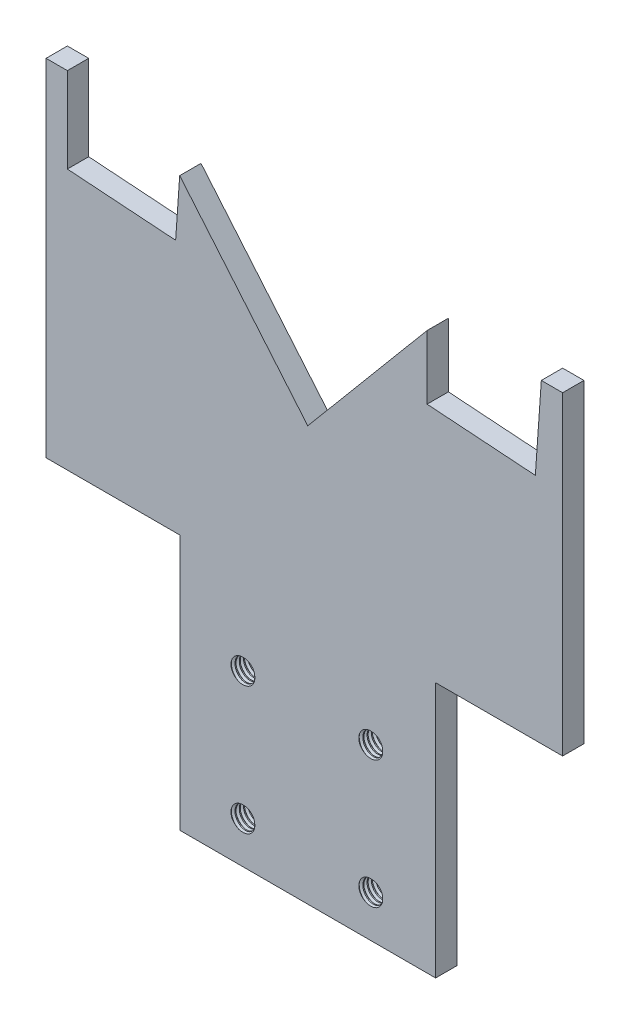
SolidWorks part; units mm, degrees
ref_plane "Front Plane" through (0, 0, 0) normal (0, 0, 1) x (1, 0, 0)
ref_plane "Top Plane" through (0, 0, 0) normal (0, 1, 0) x (1, 0, 0)
ref_plane "Right Plane" through (0, 0, 0) normal (1, 0, 0) x (0, 0, -1)
sketch "Sketch1" plane through (0, 0, 0) normal (0, 0, 1) x (1, 0, 0)
  line L1 (-35.9396, -69.828) -> (26.5158, -69.828)
  line L5 (0, 53.616) -> (35.56, 95.9948)
  line L6 (-39.37, 81.81) -> (-38.1613, 99.0949)
  line L7 (0, -55) -> (0, 55) construction
  line L10 (35.56, 95.9948) -> (35.56, 76.984)
  line L11 (35.56, 76.984) -> (67.818, 74.7283)
  line L12 (67.818, 74.7283) -> (69.5941, 100.1283)
  line L13 (69.5941, 100.1283) -> (75.9441, 100.1283)
  line L14 (26.5158, -69.828) -> (75.9441, -69.828)
  line L15 (75.9441, -69.828) -> (75.9441, 100.1283)
  line L18 (-39.37, 81.81) -> (-71.628, 84.0657)
  line L19 (-71.628, 84.0657) -> (-71.628, 109.4657)
  line L20 (-71.628, 109.4657) -> (-77.978, 109.4657)
  line L21 (-77.978, 109.4657) -> (-77.978, -69.828)
  line L22 (-77.978, -69.828) -> (-35.9396, -69.828)
  line L23 (0, 53.616) -> (-38.1613, 99.0949)
  point P0 (0, 0)
  dimension "D2" = 40
  dimension "D3" = 123.444
  dimension "D4" = 4
  dimension "D5" = 4
  dimension "D6" = 90
  dimension "D7" = 94
  dimension "D8" = 32.258
  dimension "D9" = 32.258
  dimension "D10" = 4
  dimension "D11" = 35.56
  dimension "D12" = 39.37
  dimension "D13" = 146.812
  dimension "D14" = 151.638
  dimension "D15" = 90
  dimension "D16" = 40
  dimension "D17" = 25.4
  dimension "D18" = 25.4
  dimension "D19" = 6.35
  dimension "D20" = 6.35
extrude "Boss-Extrude1" add sketch "Sketch1" along normal blind 6.35
ref_axis "Axis1" through (0, -69.828, 6.35) along (0, 1, 0)
sketch "Sketch2" plane through (0, 0, 6.35) normal (0, 0, 1) x (1, 0, 0)
  line L0 (0, -69.828) -> (0, 53.616) construction
  line L1 (-77.978, -69.828) -> (75.9441, -69.828) construction
  circle A0 centre (19.05, -57.128) radius 3.2639
  dimension "D1" = 19.05
  dimension "D2" = 12.7
extrude "Cut-Extrude1" cut sketch "Sketch2" against normal through all
pattern_linear "LPattern1" count 2 spacing 38.1 along (0, 1, 0) count 2 spacing 38.1 along (-1, 0, 0) of "Cut-Extrude1"
thread "Thread1" pitch 1.27 method cut profile "Thread Profile1" start angle 0, offset 0, length 0, pitch 1.27, diameter 6.5278
ref_plane "Plane1" through (22.3139, -57.128, 0) normal (0, -1, 0) x (1, 0, 0)
sketch "Thread Profile1" plane through (22.3139, -57.128, 0) normal (0, -1, 0) x (1, 0, 0)
  line L0 (0, 0) -> (0, 1.27) construction
  line L1 (0, 0) -> (0.6874, 0.3969)
  line L2 (0.6874, 0.3969) -> (0.6874, 0.5556)
  line L3 (0.6874, 0.5556) -> (0, 0.9525)
  line L4 (0.6874, 0.4762) -> (0, 0.4762) construction
  line L11 (0, 0) -> (0, 0.9525)
  point P2 (0, 0)
  dimension "Pitch" = 1.27
  dimension "Profile_Angle" = 60
  dimension "Profile_Land" = 0.1588
  dimension "Profile_Height" = 0.6874
pattern_linear "LPattern2" count 2 spacing 38.1 along (0, 1, 0) count 2 spacing 38.1 along (-1, 0, 0) of "Thread1"
sketch "Sketch3" plane through (0, 0, 6.35) normal (0, 0, 1) x (1, 0, 0)
  line L5 (-77.978, -69.828) -> (-38.1, -69.828)
  line L6 (-77.978, -69.828) -> (75.9441, -69.828) construction
  line L7 (-38.1, -69.828) -> (-38.1, 6.372)
  line L8 (-38.1, 6.372) -> (-77.978, 6.372)
  line L9 (-77.978, 109.4657) -> (-77.978, -69.828) construction
  line L10 (-77.978, 6.372) -> (-77.978, -69.828)
  line L11 (38.1, -69.828) -> (75.9441, -69.828)
  line L12 (75.9441, -69.828) -> (75.9441, 6.372)
  line L13 (75.9441, -69.828) -> (75.9441, 100.1283) construction
  line L14 (75.9441, 6.372) -> (38.1, 6.372)
  line L15 (38.1, 6.372) -> (38.1, -69.828)
  line L16 (0, -69.828) -> (0, 53.616) construction
  dimension "D1" = 76.2
  dimension "D2" = 38.1
  dimension "D3" = 76.2
  dimension "D4" = 76.2
extrude "Cut-Extrude2" cut sketch "Sketch3" against normal through all
